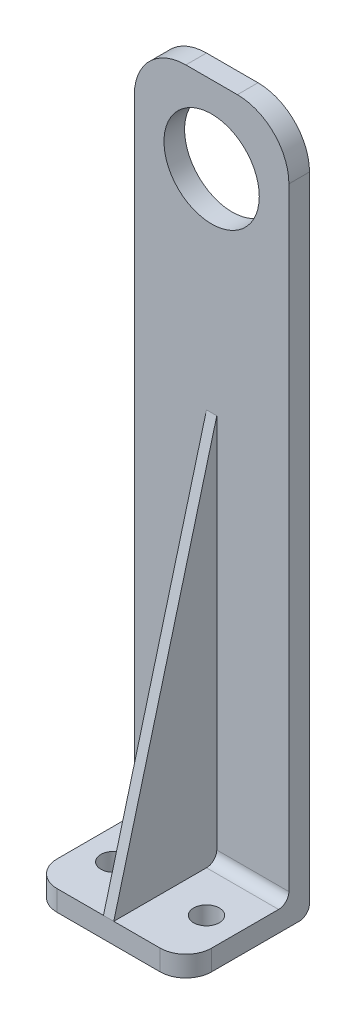
SolidWorks part; units mm, degrees
ref_plane "정면" through (0, 0, 0) normal (0, 0, 1) x (1, 0, 0)
ref_plane "윗면" through (0, 0, 0) normal (0, 1, 0) x (1, 0, 0)
ref_plane "우측면" through (0, 0, 0) normal (1, 0, 0) x (0, 0, -1)
sketch "스케치1" plane through (0, 0, 0) normal (0, 0, 1) x (1, 0, 0)
  line L0 (-15, 37.5) -> (15, 37.5) construction
  line L1 (-15, 67.5) -> (15, 67.5)
  line L2 (-15, 67.5) -> (-15, -67.5)
  line L3 (-15, -67.5) -> (15, -67.5)
  line L4 (15, 67.5) -> (15, -67.5)
  line L5 (-15, 67.5) -> (15, -67.5) construction
  line L6 (-15, -67.5) -> (15, 67.5) construction
  line L7 (0, 67.5) -> (0, 37.5) construction
  line L8 (0, 37.5) -> (0, -67.5) construction
  line L9 (-15, 17.5) -> (15, 17.5) construction
  line L11 (-15, -67.5) -> (15, -67.5)
  line L12 (-15, -67.5) -> (-15, -63.5)
  line L13 (-15, -63.5) -> (15, -63.5)
  line L14 (15, -67.5) -> (15, -63.5)
  circle A0 centre (0, 52.5) radius 9.25
  point P0 (0, 0)
  dimension "D4" = 18.5
  dimension "D1" = 35
  dimension "D2" = 30
  dimension "D3" = 30
  dimension "D5" = 85
  dimension "D6" = 4
extrude "보스-돌출1" add sketch "스케치1" along normal blind 20 contours L13 L2 L3 L4 region at (0, -65.5, 0)
extrude "보스-돌출2" add sketch "스케치1<3>" against normal blind 4 contours L2 L13 L4 L1 A0 | L13 L2 L3 L4 region at (0, -1.7077, 0) region at (0, -65.5, 0)
sketch "스케치1<3>" plane through (0, 0, 0) normal (0, 0, 1) x (1, 0, 0) same geometry as "스케치1"
sketch "스케치2" plane through (0, 0, 0) normal (1, 0, 0) x (0, 0, -1)
  line L0 (-20, -63.5) -> (0, -63.5) construction
  line L1 (0, 67.5) -> (0, -63.5) construction
  line L2 (-20, -63.5) -> (0, -63.5) construction
  line L3 (0, 67.5) -> (0, -63.5) construction
  line L4 (0, 11.5) -> (-20, -63.5)
  dimension "D1" = 75
rib "보강대3" sketch "스케치2" sketch "스케치2" thickness 2 extrusion direction parallel to sketch draft on no parameters "D1"=2
sketch "스케치3" plane through (0, -67.5, 0) normal (0, -1, 0) x (1, 0, 0)
  line L0 (-15, 10) -> (15, 10) construction
  line L1 (-15, 20) -> (-15, -4) construction
  line L2 (15, 20) -> (15, -4) construction
  line L3 (0, 20) -> (0, -4) construction
  line L4 (-15, 20) -> (15, 20) construction
  line L5 (-15, -4) -> (15, -4) construction
  circle A0 centre (-9, 10) radius 2.5
  circle A1 centre (9, 10) radius 2.5
  dimension "D3" = 5
  dimension "D1" = 18
  dimension "D2" = 9
  dimension "D4" = 10
extrude "컷-돌출1" cut sketch "스케치3" against normal blind 4
fillet "필렛1" radius 5 2 edges at (15, -65.5, 20) (-15, -65.5, 20)
fillet "필렛2" radius 2 3 edges at (8, -63.5, 0) (-8, -63.5, 0) (0, -67.5, -4)
fillet "필렛3" radius 10 2 edges at (15, 67.5, -2) (-15, 67.5, -2)
